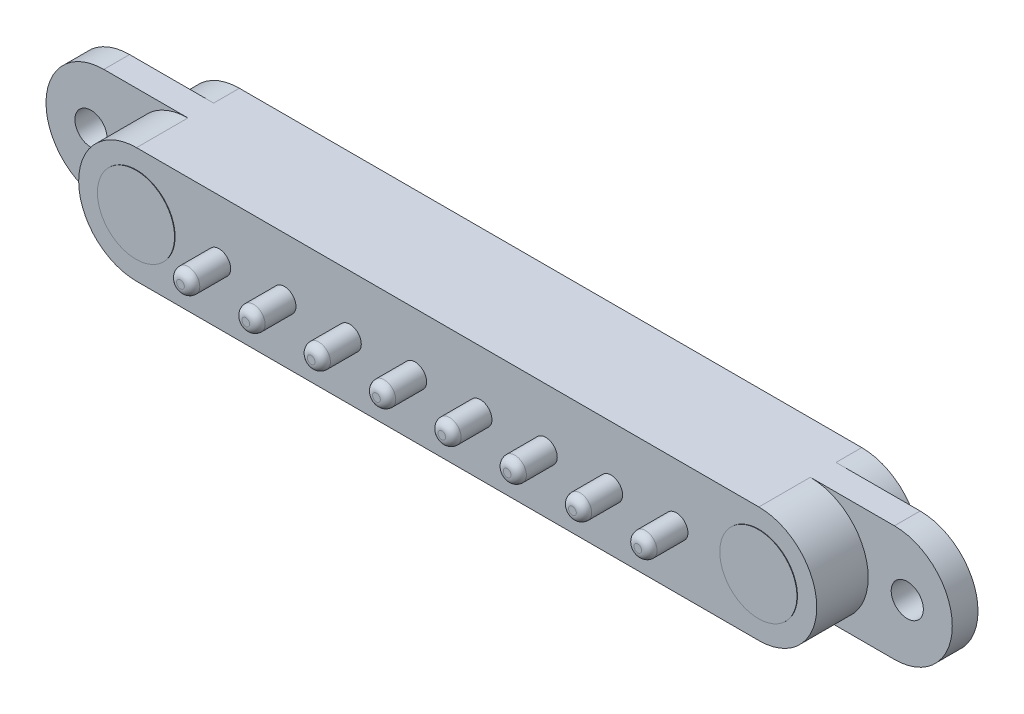
SolidWorks part; units mm, degrees
note: The reader was unsure of these and kept them because the rebuilt part matched: shared geometry of "草图2<3>".
ref_plane "前视基准面" through (0, 0, 0) normal (0, 0, 1) x (1, 0, 0)
ref_plane "上视基准面" through (0, 0, 0) normal (0, 1, 0) x (1, 0, 0)
ref_plane "右视基准面" through (0, 0, 0) normal (1, 0, 0) x (0, 0, -1)
sketch "草图2" plane through (0, 0, 0) normal (0, 0, 1) x (1, 0, 0)
  line L0 (-12.1, 0) -> (12.1, 0) construction
  line L1 (-12.1, 2.25) -> (12.1, 2.25)
  line L2 (-12.1, -2.25) -> (12.1, -2.25)
  line L3 (-15.37, 0) -> (15.37, 0) construction
  line L4 (-15.37, 2.25) -> (15.37, 2.25)
  line L5 (-15.37, -2.25) -> (15.37, -2.25)
  line L6 (0, 0) -> (0, 7.5362) construction
  arc A0 (-12.1, 2.25) -> (-12.1, -2.25) centre (-12.1, 0) ccw
  arc A1 (12.1, -2.25) -> (12.1, 2.25) centre (12.1, 0) ccw
  arc A2 (-15.37, 2.25) -> (-15.37, -2.25) centre (-15.37, 0) ccw
  arc A3 (15.37, -2.25) -> (15.37, 2.25) centre (15.37, 0) ccw
  circle A6 centre (-15.87, 0) radius 0.625
  circle A7 centre (15.87, 0) radius 0.625
  point P2 (0, 0)
  point P10 (0, 0)
  dimension "D5" = 31.74
  dimension "D6" = 1.25
  dimension "D1" = 4.5
  dimension "D2" = 24.2
  dimension "D3" = 30.74
  dimension "D4" = 4.5
  dimension "D7" = 0
extrude "凸台-拉伸1" add sketch "草图2" against normal blind 4 contours A0 L2 A1 L1
extrude "凸台-拉伸2" add sketch "草图2<3>" against normal blind 1 from offset 2 contours A2 L5 A3 L4 | A6 | A7 offset against normal yes
sketch "草图2<3>" plane through (0, 0, 0) normal (0, 0, 1) x (1, 0, 0) same geometry as "草图2"
sketch "草图4" plane through (0, 0, -4) normal (0, 0, -1) x (-1, 0, 0)
  line L0 (-18.0926, 0) -> (19.6809, 0) construction
  line L1 (0, 0) -> (0, 5.1514) construction
  line L2 (-8.89, 0) -> (-6.35, 0) construction
  circle A0 centre (-8.89, 0) radius 0.45
  circle A1 centre (-6.35, 0) radius 0.45
  circle A2 centre (-3.81, 0) radius 0.45
  circle A3 centre (-1.27, 0) radius 0.45
  circle A4 centre (1.27, 0) radius 0.45
  circle A5 centre (3.81, 0) radius 0.45
  circle A6 centre (6.35, 0) radius 0.45
  circle A7 centre (8.89, 0) radius 0.45
  dimension "D1" = 0.9
  dimension "D3" = 8
  dimension "D2" = 8.89
  dimension "D4" = 2.54
extrude "凸台-拉伸3" add sketch "草图4" along normal blind 1.5 and the other way offset from surface (5.5 mm away) 1.5 other way up to face at (0, 0, 0)
sketch "草图5" plane through (0, 0, 0) normal (0, 0, 1) x (1, 0, 0)
  line L0 (-18.8071, 0) -> (20.7184, 0) construction
  line L1 (0, 0) -> (0, 5.8863) construction
  circle A0 centre (-12.1, 0) radius 1.5
  circle A1 centre (12.1, 0) radius 1.5
  dimension "D1" = 24.2
  dimension "D2" = 3
extrude "凸台-拉伸4" add sketch "草图5" along normal blind 0.02
fillet "圆角1" radius 0.3 8 edges at (9.34, 0, 1.5) (6.8, 0, 1.5) (4.26, 0, 1.5) (1.72, 0, 1.5) (-0.82, 0, 1.5) (-3.36, 0, 1.5) (-5.9, 0, 1.5) (-8.44, 0, 1.5)
